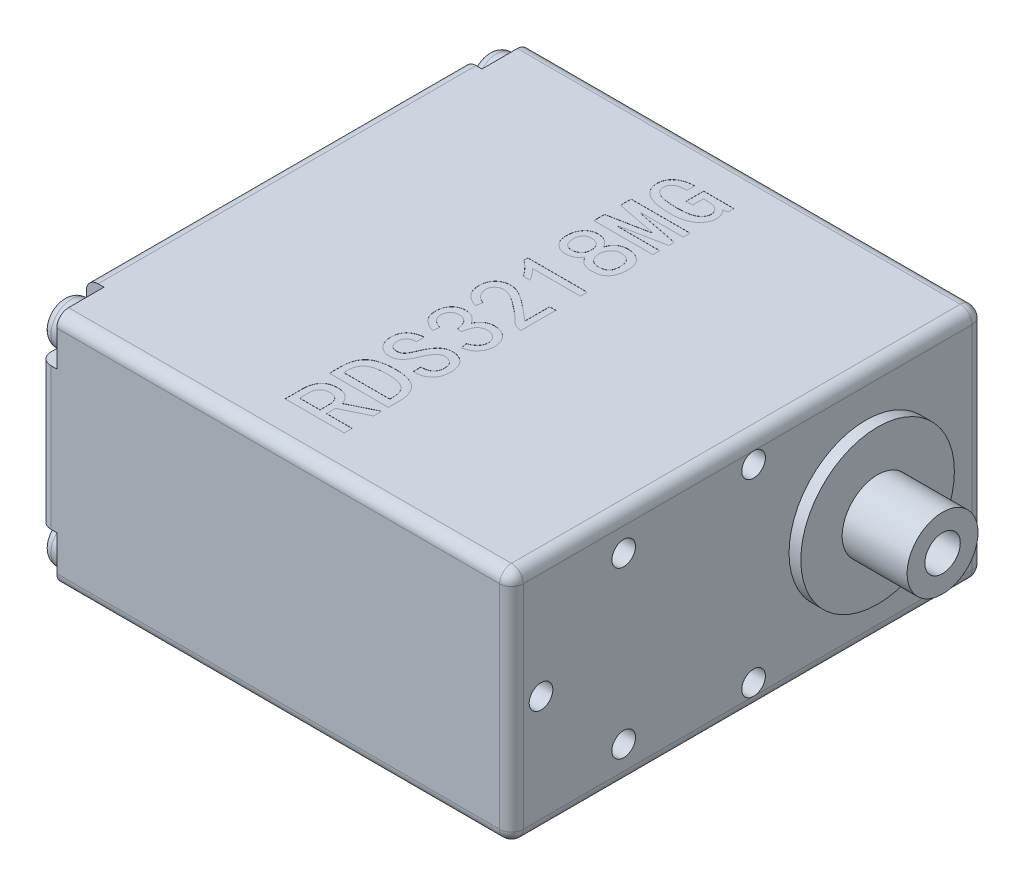
SolidWorks part; units mm, degrees
ref_plane "前视基准面" through (0, 0, 0) normal (0, 0, 1) x (1, 0, 0)
ref_plane "上视基准面" through (0, 0, 0) normal (0, 1, 0) x (1, 0, 0)
ref_plane "右视基准面" through (0, 0, 0) normal (1, 0, 0) x (0, 0, -1)
sketch "草图1" plane through (0, 0, 0) normal (0, 1, 0) x (1, 0, 0)
  line L1 (-20, 20) -> (20, 20)
  line L2 (-20, 20) -> (-20, -20)
  line L3 (-20, -20) -> (20, -20)
  line L4 (20, 20) -> (20, -20)
  line L5 (-20, 20) -> (20, -20) construction
  line L6 (-20, -20) -> (20, 20) construction
  point P0 (0, 0)
  dimension "D1" = 40
  dimension "D2" = 40
extrude "凸台-拉伸1" add sketch "草图1" along normal blind 20
sketch "草图3" plane through (20, 0, 0) normal (1, 0, 0) x (0, 0, -1)
  line L1 (-20, 20) -> (-20, 0) construction
  line L2 (20, 10) -> (-20, 10) construction
  line L3 (20, 20) -> (20, 0) construction
  line L4 (-20, 20) -> (-20, 0) construction
  circle A0 centre (10, 10) radius 6.5
  dimension "D2" = 30
  dimension "D3" = 13
extrude "凸台-拉伸2" add sketch "草图3" along normal blind 1
sketch "草图4" plane through (21, 0, 0) normal (1, 0, 0) x (0, 0, -1)
  circle A0 centre (10, 10) radius 3
extrude "凸台-拉伸3" add sketch "草图4" along normal blind 5.5
sketch "草图5" plane through (26.5, 0, 0) normal (1, 0, 0) x (0, 0, -1)
  circle A0 centre (10, 10) radius 1.5
extrude "切除-拉伸2" cut sketch "草图5" against normal blind 3.5
sketch "草图6" plane through (-20, 0, 0) normal (-1, 0, 0) x (0, 0, 1)
  line L0 (-20, 20) -> (20, 0) construction
  line L1 (20, 20) -> (16, 20)
  line L2 (20, 20) -> (20, 16)
  line L3 (20, 16) -> (16, 16)
  line L4 (16, 20) -> (16, 16)
  line L5 (-20, 0) -> (20, 20) construction
  line L6 (0, 10) -> (20, 10) construction
  line L7 (20, 20) -> (20, 0) construction
  line L8 (20, 10) -> (-20, 10) construction
  line L9 (-20, 20) -> (-20, 0) construction
  line L10 (-20, 10) -> (0, 10) construction
  line L11 (0, 10) -> (0, 20) construction
  line L12 (-20, 20) -> (20, 20) construction
  line L13 (0, 20) -> (0, 0) construction
  line L14 (-16, 20) -> (-16, 16)
  line L15 (-20, 16) -> (-16, 16)
  line L16 (-20, 20) -> (-20, 16)
  line L17 (-20, 20) -> (-16, 20)
  line L18 (-20, 0) -> (-16, 0)
  line L19 (-20, 0) -> (-20, 4)
  line L20 (-20, 4) -> (-16, 4)
  line L21 (-16, 0) -> (-16, 4)
  line L22 (16, 0) -> (16, 4)
  line L23 (20, 4) -> (16, 4)
  line L24 (20, 0) -> (20, 4)
  line L25 (20, 0) -> (16, 0)
  dimension "D1" = 4
  dimension "D2" = 4
extrude "切除-拉伸3" cut sketch "草图6" against normal blind 1.5
fillet "圆角1" radius 2 4 edges at (-19.25, 16, -16) (-19.25, 16, 16) (-19.25, 4, 16) (-19.25, 4, -16)
extrude "凸台-拉伸4" add sketch "草图3<2>" against normal blind 41
sketch "草图3<2>" plane through (20, 0, 0) normal (1, 0, 0) x (0, 0, -1) same geometry as "草图3"
sketch "草图7" plane through (-20, 0, 0) normal (-1, 0, 0) x (0, 0, 1)
  line L1 (20, 16) -> (20, 4) construction
  line L2 (10.5, 0) -> (10.5, 20) construction
  line L4 (-16, 0) -> (16, 0) construction
  line L5 (-16, 20) -> (16, 20) construction
  line L8 (20, 10) -> (10.5, 10) construction
  circle A3 centre (-0.5, 18) radius 1
  circle A4 centre (17.5, 10) radius 1
  circle A5 centre (10.5, 17) radius 1
  circle A7 centre (-0.5, 2) radius 1
  circle A8 centre (10.5, 3) radius 1
  dimension "D1" = 9.5
  dimension "D2" = 2
  dimension "D3" = 14
  dimension "D4" = 16
  dimension "D5" = 20.5
  dimension "D8" = 2.5
extrude "切除-拉伸4" cut sketch "草图7" against normal blind 5
extrude "凸台-拉伸5" add sketch "草图4<2>" against normal blind 46
sketch "草图4<2>" plane through (21, 0, 0) normal (1, 0, 0) x (0, 0, -1) same geometry as "草图4"
sketch "草图8" plane through (-25, 0, 0) normal (-1, 0, 0) x (0, 0, 1)
  circle A0 centre (-10, 10) radius 1.5
extrude "切除-拉伸5" cut sketch "草图8" against normal blind 4
sketch "草图9" plane through (-18.5, 0, 0) normal (-1, 0, 0) x (0, 0, 1)
  line L0 (-20, 20) -> (-18, 18) construction
  line L1 (0, 0) -> (0, 20) construction
  line L2 (-16, 20) -> (-20, 16) construction
  line L3 (-16, 20) -> (16, 20) construction
  line L4 (0, 10) -> (-20, 10) construction
  line L5 (-20, 16) -> (-20, 4) construction
  line L6 (-20, 10) -> (20, 10) construction
  line L7 (20, 16) -> (20, 4) construction
  line L8 (16, 20) -> (20, 16) construction
  line L9 (20, 20) -> (18, 18) construction
  circle A0 centre (-18, 18) radius 1.75
  circle A1 centre (-18, 2) radius 1.75
  circle A2 centre (18, 2) radius 1.75
  circle A3 centre (18, 18) radius 1.75
  dimension "D1" = 3.5
extrude "凸台-拉伸6" add sketch "草图9" along normal blind 1.5
fillet "圆角3" radius 0.75 4 edges at (-20, 18, -16.25) (-20, 2, -19.75) (-20, 18, 16.25) (-20, 2, 19.75)
fillet "圆角4" radius 1 12 edges at (-20, 10, 20) (-20, 0, 0) (-20, 20, 0) (-20, 10, -20) (20, 10, -20) (20, 10, 20) (20, 20, 0) (20, 0, 0) (0.75, 0, 20) (0.75, 20, 20) (0.75, 20, -20) (0.75, 0, -20)
sketch "草图10" plane through (0, 20, 0) normal (0, 1, 0) x (1, 0, 0)
  line L0 (2.5, -19) -> (2.5, 19) construction
  line L1 (-18.5, -19) -> (19, -19) construction
  line L2 (19, 19) -> (-18.5, 19) construction
  text T0 "RDS3218MG" font "黑体" height 5
  dimension "D1" = 2.5
extrude "切除-拉伸6" cut sketch "草图10" against normal blind 0.01
sketch "草图11" plane through (20, 0, 0) normal (1, 0, 0) x (0, 0, -1)
  line L0 (-20, 10) -> (49980, 10) construction
  line L1 (-20, 1) -> (-20, 19) construction
  circle A0 centre (-17.5, 10) radius 1
  circle A1 centre (-10.5, 17) radius 1
  circle A2 centre (0.5, 18) radius 1
  circle A3 centre (0.5, 2) radius 1
  circle A4 centre (-10.5, 3) radius 1
  point P4 (-20, 10)
  dimension "D1" = 2
  dimension "D2" = 2.5
  dimension "D3" = 9.5
  dimension "D4" = 20.5
  dimension "D5" = 14
  dimension "D6" = 16
extrude "切除-拉伸7" cut sketch "草图11" against normal blind 5
